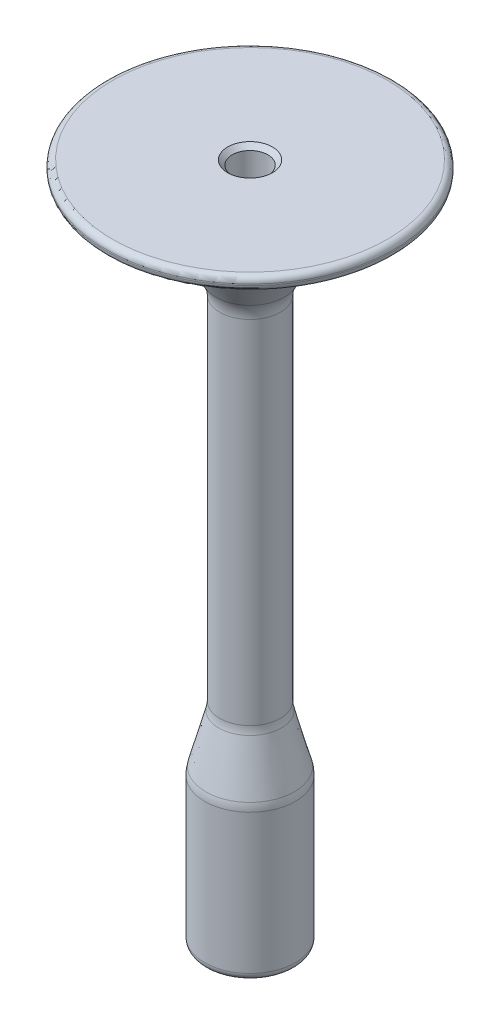
SolidWorks part; units mm, degrees
ref_plane "Front Plane" through (0, 0, 0) normal (0, 0, 1) x (1, 0, 0)
ref_plane "Top Plane" through (0, 0, 0) normal (0, 1, 0) x (1, 0, 0)
ref_plane "Right Plane" through (0, 0, 0) normal (1, 0, 0) x (0, 0, -1)
sketch "Sketch1" plane through (0, 0, 0) normal (0, 0, 1) x (1, 0, 0)
  line L1 (-5.08, 96.012) -> (-5.08, 34.8794)
  line L3 (-5.08, 0) -> (-5.08, 22.86)
  line L4 (-5.08, 22.86) -> (0, 22.86)
  line L5 (0, 22.86) -> (0, 105.3)
  line L6 (0, 105.3) -> (-3, 105.3)
  line L7 (-3, 105.3) -> (-3, 114.3)
  line L8 (-3, 114.3) -> (-24.13, 114.3)
  line L9 (-7.62, 100.4114) -> (0, 100.4114) construction
  line L10 (-11.2862, 106.7614) -> (0, 106.7614) construction
  line L11 (-5.08, 96.012) -> (-12.6967, 109.2044)
  line L12 (-12.6967, 109.2044) -> (-24.13, 112.268)
  line L13 (-24.13, 112.268) -> (-24.13, 114.3)
  line L14 (-5.08, 34.8794) -> (-7.62, 25.4)
  line L15 (-7.62, 25.4) -> (-7.62, 0)
  line L16 (-7.62, 0) -> (-5.08, 0)
  line L17 (-5.08, 0) -> (0, 0) construction
  dimension "D1" = 3
  dimension "D2" = 9
  dimension "D3" = 24.13
  dimension "D4" = 5.08
  dimension "D5" = 114.3
  dimension "D6" = 30
  dimension "D7" = 5.08
  dimension "D8" = 75
  dimension "D9" = 6.35
  dimension "D10" = 7.62
  dimension "D11" = 2.032
  dimension "D12" = 7.62
  dimension "D13" = 25.4
  dimension "D14" = 22.86
  dimension "D15" = 18.288
revolve "Revolve1" add sketch "Sketch1" angle 360 about L5
chamfer "Chamfer1" distance 0.762 angle 45 1 edges at (0, 114.3, -3)
fillet "Fillet1" radius 1.27 2 edges at (0, 0, -7.62) (0, 0, -5.08)
fillet "Fillet2" radius 1.016 2 edges at (0, 114.3, -24.13) (0, 112.268, -24.13)
fillet "Fillet3" radius 5.08 4 edges at (0, 25.4, -7.62) (0, 34.8794, -5.08) (0, 96.012, -5.08) (0, 109.2044, -12.6967)
